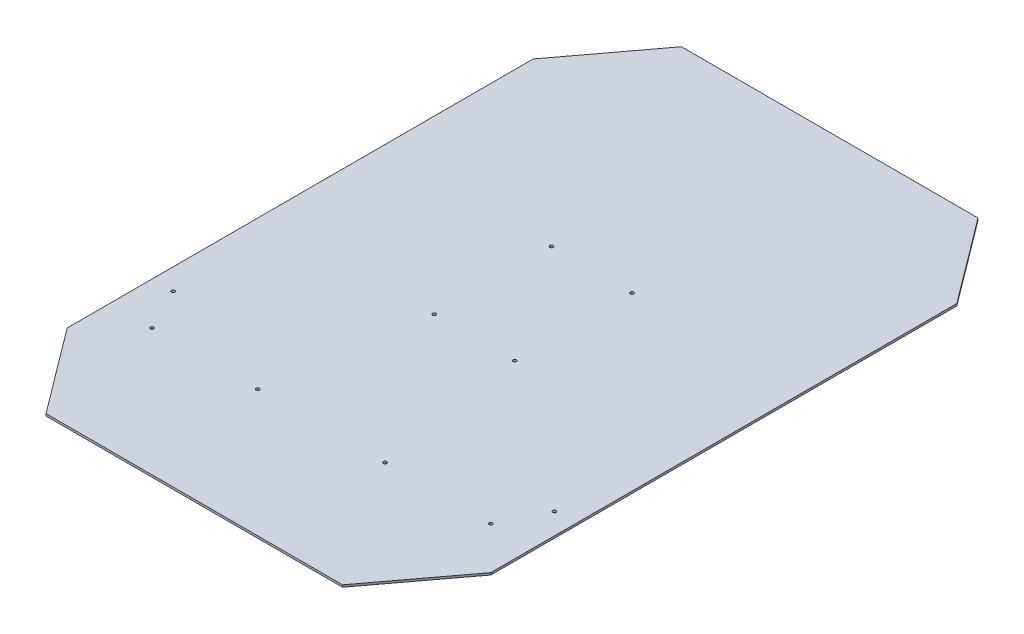
SolidWorks part; units mm, degrees
ref_plane "Front Plane" through (0, 0, 0) normal (0, 0, 1) x (1, 0, 0)
ref_plane "Top Plane" through (0, 0, 0) normal (0, 1, 0) x (1, 0, 0)
ref_plane "Right Plane" through (0, 0, 0) normal (1, 0, 0) x (0, 0, -1)
sketch "Sketch1" plane through (0, 0, 0) normal (0, 1, 0) x (1, 0, 0)
  line L0 (-500, 550) -> (-350, 750)
  line L1 (-500, 750) -> (500, 750)
  line L2 (-500, 750) -> (-500, -750)
  line L3 (-500, -750) -> (500, -750)
  line L4 (500, 750) -> (500, -750)
  line L5 (-500, 750) -> (500, -750) construction
  line L6 (-500, -750) -> (500, 750) construction
  line L7 (0, 750) -> (0, -750) construction
  line L8 (-500, 0) -> (500, 0) construction
  line L9 (500, 550) -> (350, 750)
  line L10 (500, -550) -> (350, -750)
  line L11 (-500, -550) -> (-350, -750)
  point P0 (0, 0)
  dimension "D1" = 1500
  dimension "D2" = 1000
  dimension "D3" = 200
  dimension "D4" = 150
extrude "Boss-Extrude1" add sketch "Sketch1" along normal blind 5 contours L2 L11 L3 L10 L4 L9 L1 L0 region at (0, 0, 0)
sketch "Sketch2" plane through (0, 5, 0) normal (0, 1, 0) x (1, 0, 0)
  line L0 (0, 750) -> (0, -750) construction
  line L1 (-350, 750) -> (350, 750) construction
  line L2 (-350, -750) -> (350, -750) construction
  line L3 (-500, 50) -> (500, 50) construction
  line L4 (-500, 550) -> (-500, -550) construction
  line L5 (500, 550) -> (500, -550) construction
  circle A0 centre (95, 188.5) radius 4
  circle A1 centre (-95, 188.5) radius 4
  circle A2 centre (95, -88.5) radius 4
  circle A3 centre (-95, -88.5) radius 4
  dimension "D2" = 8
  dimension "D1" = 700
  dimension "D3" = 95
  dimension "D4" = 138.5
extrude "Cut-Extrude1" cut sketch "Sketch2" against normal through all
sketch "Sketch3" plane through (0, 0, 0) normal (0, -1, 0) x (1, 0, 0)
  line L0 (0, 750) -> (0, 450) construction
  line L1 (-350, 750) -> (350, 750) construction
  line L2 (-400, 450) -> (400, 450) construction
  line L3 (-350, -750) -> (350, -750) construction
  circle A0 centre (-400, 450) radius 4
  circle A1 centre (-450, 350) radius 4
  circle A2 centre (-150, 450) radius 4
  circle A3 centre (450, 350) radius 4
  circle A4 centre (150, 450) radius 4
  circle A5 centre (400, 450) radius 4
  dimension "D4" = 8
  dimension "D1" = 400
  dimension "D2" = 450
  dimension "D3" = 1200
  dimension "D5" = 100
  dimension "D6" = 150
extrude "Cut-Extrude2" cut sketch "Sketch3" against normal blind 10
